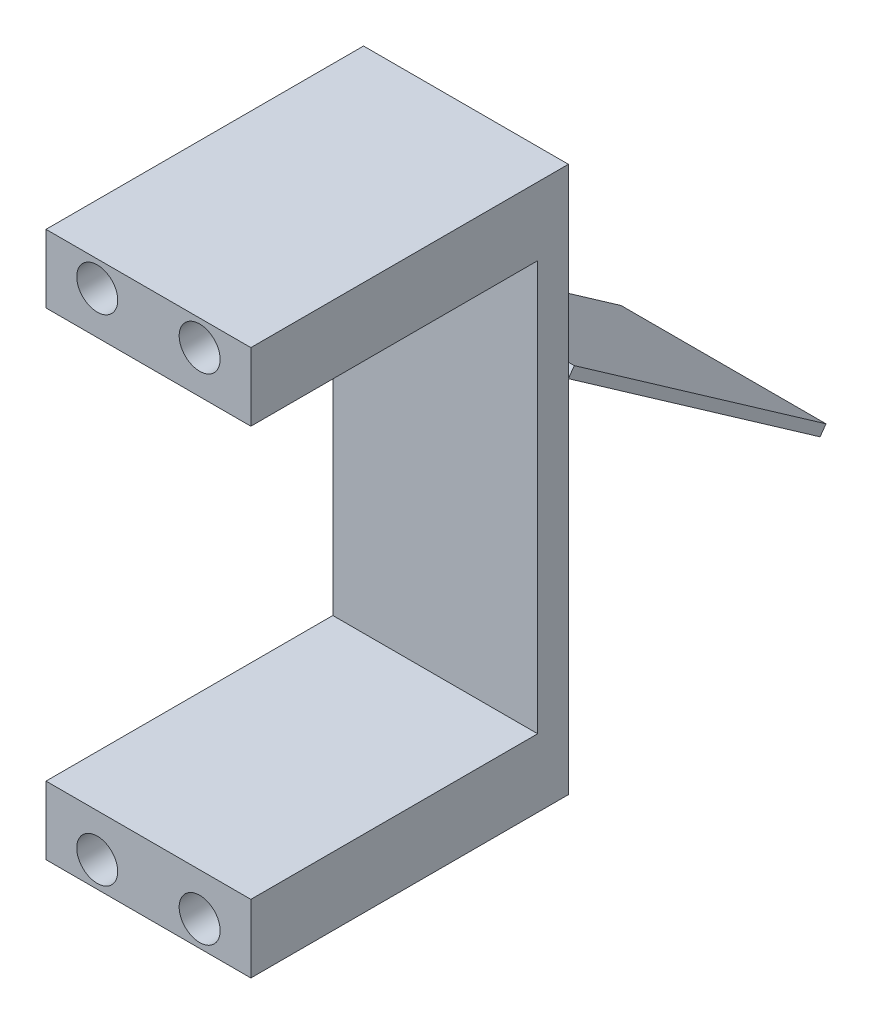
SolidWorks part; units mm, degrees
ref_plane "Front Plane" through (0, 0, 0) normal (0, 0, 1) x (1, 0, 0)
ref_plane "Top Plane" through (0, 0, 0) normal (0, 1, 0) x (1, 0, 0)
ref_plane "Right Plane" through (0, 0, 0) normal (1, 0, 0) x (0, 0, -1)
sketch "Sketch3" plane through (0, 0, 0) normal (0, 0, 1) x (1, 0, 0)
  line L1 (-7.2656, 26.4783) -> (-17.2656, 26.4783)
  line L2 (2.7344, -0.1717) -> (-17.2656, -0.1717)
  line L3 (-7.2656, -0.1717) -> (-7.2656, 53.1283)
  line L4 (2.7344, 53.1283) -> (-17.2656, 53.1283)
  line L5 (-17.2656, -0.1717) -> (-17.2656, 53.1283)
  line L6 (-12.2656, 26.4783) -> (-12.2656, 6.4783)
  line L7 (-7.2656, 6.4783) -> (-17.2656, 6.4783)
  line L8 (2.7344, 46.4783) -> (-17.2656, 46.4783)
  line L9 (-7.2656, 6.4783) -> (2.7344, 6.4783)
  line L10 (2.7344, -0.1717) -> (2.7344, 53.1283)
  line L11 (2.7344, -0.1717) -> (-2.2656, -0.1717)
  line L12 (2.7344, -0.1717) -> (2.7344, 2.3283)
  line L13 (2.7344, 2.3283) -> (-2.2656, 2.3283)
  line L14 (-2.2656, -0.1717) -> (-2.2656, 2.3283)
  circle A0 centre (-2.2656, 2.3283) radius 2
  circle A1 centre (-12.2656, 2.3283) radius 2
  circle A2 centre (-12.2656, 50.6283) radius 2
  circle A3 centre (-2.2656, 50.6283) radius 2
  point P0 (-2.2655, 2.3283)
  point P13 (-12.2656, 6.4783)
  point P16 (-7.2656, 46.4783)
  point P29 (0, 0)
  point P30 (5.6477, -1.6029)
  dimension "D7" = 4
  dimension "D2" = 10
  dimension "D3" = 53.3
  dimension "D4" = 20
  dimension "D5" = 2.5
  dimension "D6" = 5
extrude "Boss-Extrude1" add sketch "Sketch3" along normal blind 3 contours L3 L8 L5 L1 | L9 L10 L8 L3 | L7 L6 L1 L5 | L7 L3 L1 L6 region at (-9.7656, 16.4783, 0) region at (-2.2656, 26.4783, 0) region at (-12.2656, 36.4783, 0) region at (-14.7656, 16.4783, 0)
extrude "Boss-Extrude2" add sketch "Sketch3<3>" along normal blind 31 contours L8 L3 L4 L5 A2 | L8 L10 L4 L3 A3 | L3 L7 L5 L2 A1 | A0 L13 L10 L9 L3 L2 L14 | A0 L14 L2 L10 L13 region at (-2.2656, 6.3582, 0) region at (-7.3857, 3.1533, 0) region at (-12.2656, 46.5984, 0) region at (-7.1455, 49.8033, 0) region at (0.7887, 0.9437, 0)
sketch "Sketch3<3>" plane through (0, 0, 0) normal (0, 0, 1) x (1, 0, 0) same geometry as "Sketch3"
ref_plane "Plane3" through (0, 35, 0) normal (0, 1, 0) x (1, 0, 0)
sketch "Sketch7" plane through (0, 35, 0) normal (0, 1, 0) x (1, 0, 0)
  line L0 (-17.6608, 0) -> (3.0017, 0)
ref_plane "Plane4" through (0, 23.4854, -16.4446) normal (0, 0.8192, -0.5736) x (1, 0, 0)
sketch "Sketch8" plane through (0, 23.4854, -16.4446) normal (0, 0.8192, -0.5736) x (1, 0, 0)
  line L0 (-17.6608, -20.0752) -> (3.0017, -20.0752) construction
  line L1 (-17.2656, -20.0752) -> (2.7344, -20.0752)
  line L2 (-17.2656, -20.0752) -> (-17.2656, 9.9248)
  line L3 (-17.2656, 9.9248) -> (2.7344, 9.9248)
  line L4 (2.7344, -20.0752) -> (2.7344, 9.9248)
  line L5 (-17.2656, 0.0985) -> (-17.2656, -30.4732) construction
  line L6 (2.7344, 0.0985) -> (2.7344, -30.4732) construction
  dimension "D1" = 30
extrude "Boss-Extrude6" add sketch "Sketch8" along normal blind 1 separate body
equation "\"Servo Width\"= 20"
equation "\"Servo Height\"= 40"
equation "\"Ring Height\"= 16"
equation "\"Middle Height\"= 21"
equation "\"Pointer Height\"= 11"
equation "\"Finger Gap\"= 18"
equation "\"Servo Total Height\"= 53.3"
equation "\"Servo Screw Height\"= 2.5"
equation "\"Servo Screw Width\"= 5"
equation "\"Servo Screw Diameter\"= 4"
equation "\"Length\"= 54"
equation "\"Thinkness\"= 10"
equation "\"Take away amount\"= 7"
equation "\"Curve\"= 5deg"
equation "\"Thumb Plane Angle\"= 45deg"
equation "\"Thumb Distance\"= 10"
equation "\"Top Screw Plate Distance\"= 4"
